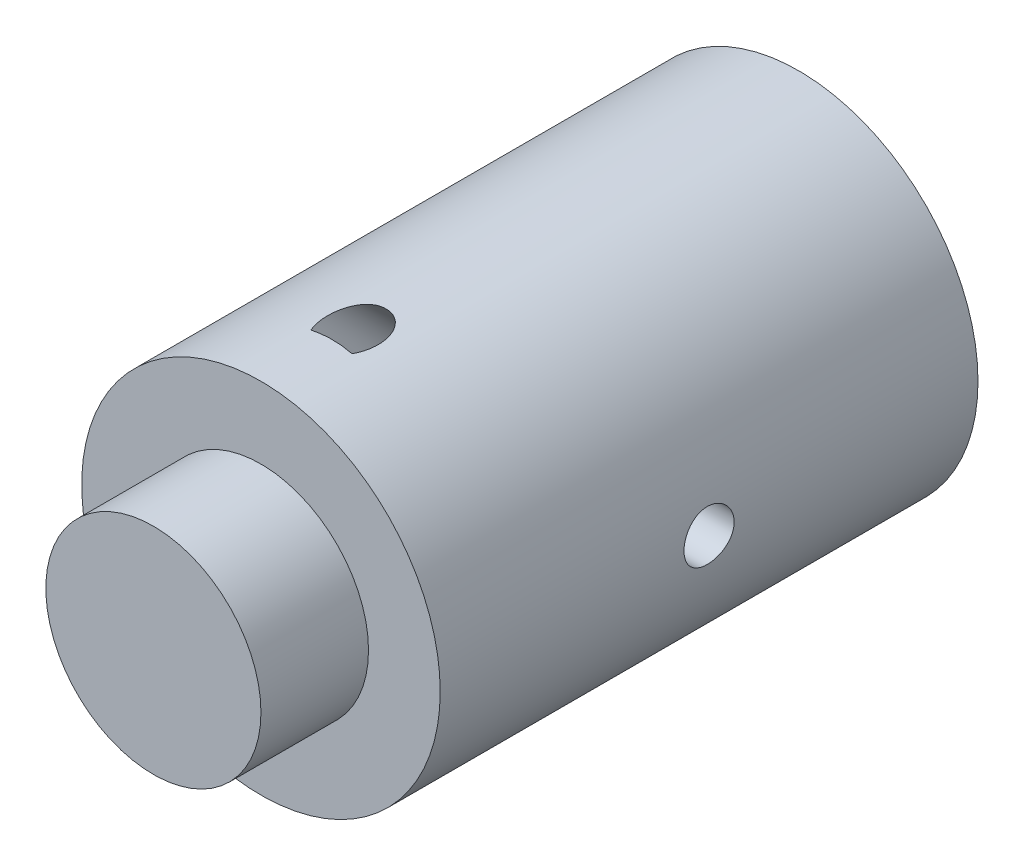
SolidWorks part; units mm, degrees
ref_plane "Front Plane" through (0, 0, 0) normal (0, 0, 1) x (1, 0, 0)
ref_plane "Top Plane" through (0, 0, 0) normal (0, 1, 0) x (1, 0, 0)
ref_plane "Right Plane" through (0, 0, 0) normal (1, 0, 0) x (0, 0, -1)
sketch "Sketch1" plane through (0, 0, 0) normal (0, 0, 1) x (1, 0, 0)
  circle A0 centre (0, 0) radius 25
  dimension "D1" = 50
extrude "Boss-Extrude1" add sketch "Sketch1" along normal blind 75 contours A0
sketch "Sketch2" plane through (0, 0, 75) normal (0, 0, 1) x (1, 0, 0)
  circle A0 centre (0, 0) radius 15
  dimension "D1" = 30
extrude "Boss-Extrude2" add sketch "Sketch2" along normal blind 15
sketch "Sketch3" plane through (0, 0, 0) normal (1, 0, 0) x (0, 0, -1)
  line L0 (-75, 0) -> (0, 0) construction
  line L1 (-75, 25) -> (-75, -25) construction
  circle A0 centre (-37.5, 0) radius 3.3
  dimension "D1" = 6.6
extrude "Cut-Extrude1" cut sketch "Sketch3" against normal blind 50 and the other way blind 50 contours A0
ref_plane "Plane1" through (0, 0, 0) normal (0, 0.7071, -0.7071) x (-1, 0, 0)
ref_axis "Axis1" through (25, 0, 37.5) along (-1, 0, 0)
sketch "Sketch4" plane through (0, 0, 0) normal (0, 0.7071, -0.7071) x (-1, 0, 0)
  line L0 (-25, 26.5165) -> (25, 26.5165) construction
  circle A0 centre (0, 26.5165) radius 4.8549
ref_plane "Plane2" through (0, -18.75, 18.75) normal (0, 0.7071, -0.7071) x (-1, 0, 0)
sketch "Sketch5" plane through (0, 0, 0) normal (1, 0, 0) x (0, 0, -1)
  circle A0 centre (-37.5, 0) radius 3.5
  dimension "D1" = 7
extrude "Cut-Extrude2" cut sketch "Sketch5" against normal blind 100 and the other way blind 100 contours A0
sketch "Sketch7" plane through (0, -18.75, 18.75) normal (0, 0.7071, -0.7071) x (-1, 0, 0)
  line L1 (-25, 26.5165) -> (25, 26.5165) construction
  line L2 (-11.127, 26.5165) -> (-39.1239, 26.5165) construction
  line L3 (0, 92.4937) -> (0, 34.7855) construction
  spline S0 degree 3 poles (-25.1254, 26.5165) (-13.46, 26.5165) (0, 27.572) (0, 63.6396) knots 0 0 0 0 1 1 1 1
sweep "Cut-Sweep1" cut path "Sketch7" circular profile diameter 7 parameters "D3"=7
mirror "Mirror1" about plane through (0, 0, 0) normal (1, 0, 0) of "Cut-Sweep1"
